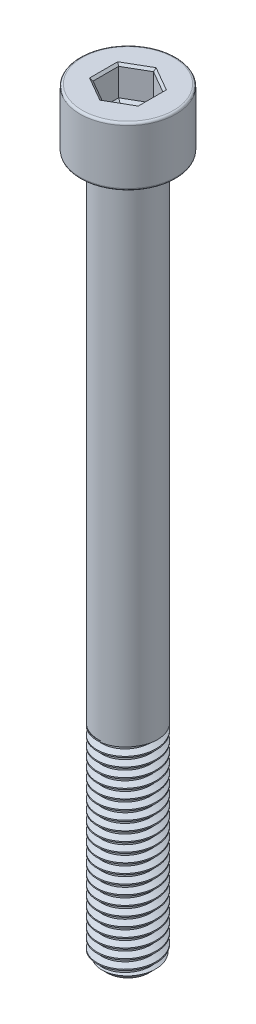
SolidWorks part; units mm, degrees
material "AISI Type A2 Tool Steel"
ref_plane "Front Plane" through (0, 0, 0) normal (0, 0, 1) x (1, 0, 0)
ref_plane "Top Plane" through (0, 0, 0) normal (0, 1, 0) x (1, 0, 0)
ref_plane "Right Plane" through (0, 0, 0) normal (1, 0, 0) x (0, 0, -1)
sketch "Sketch1" plane through (0, 0, 0) normal (0, 1, 0) x (1, 0, 0)
  circle A0 centre (0, 0) radius 4
  dimension "D1" = 8
extrude "Boss-Extrude1" add sketch "Sketch1" along normal blind 28
thread "Thread1" pitch 1.25 method cut profile "Thread Profile1" start angle 0, offset 2, length 0, pitch 1.25, diameter 8
ref_plane "Plane1" through (-4, 30, 0) normal (0, 0, 1) x (-1, 0, 0)
sketch "Thread Profile1" plane through (-4, 30, 0) normal (0, 0, 1) x (-1, 0, 0)
  line L0 (0, 0) -> (0, 1.25) construction
  line L11 (0, 0) -> (0, 1.0937)
  line L12 (0, 1.0937) -> (-0.6766, 0.7031)
  line L13 (-0.6766, 0.7031) -> (-0.6766, 0.3906)
  line L15 (-0.6766, 0.3906) -> (0, 0)
  line L17 (-0.6766, 0.5469) -> (0, 0.5469) construction
  point P2 (0, 0)
  dimension "Pitch" = 1.25
  dimension "Profile_Angle" = 60
  dimension "Profile_Land" = 0.3125
  dimension "Profile_Height" = 0.6766
sketch "Sketch2" plane through (0, 28, 0) normal (0, 1, 0) x (1, 0, 0)
  circle A0 centre (0, 0) radius 4
  dimension "D1" = 8
extrude "Boss-Extrude2" add sketch "Sketch2" along normal blind 67
sketch "Sketch5" plane through (0, 95, 0) normal (0, 1, 0) x (1, 0, 0)
  circle A0 centre (0, 0) radius 6.5
  dimension "D1" = 13
extrude "Boss-Extrude3" add sketch "Sketch5" along normal blind 8
sketch "Sketch6" plane through (0, 0, 0) normal (0, 0, 1) x (1, 0, 0)
  line L0 (0, 0) -> (0, 0.7245) construction
  line L1 (0, 0) -> (4.01, 0) construction
  line L2 (4.01, 0) -> (4.01, 1.2)
  line L3 (4.01, 1.2) -> (2.81, 0)
  line L4 (2.81, 0) -> (4.01, 0)
  dimension "D1" = 1.2
  dimension "D2" = 45
  dimension "D3" = 4.01
revolve "Cut-Revolve1" cut sketch "Sketch6" angle 360 about L0
fillet "Fillet1" radius 0.3 2 edges at (0, 95, 6.5) (0, 103, 6.5)
sketch "Sketch7" plane through (0, 103, 0) normal (0, 1, 0) x (1, 0, 0)
  line L1 (0, 3.4641) -> (-3, 1.7321)
  line L2 (-3, 1.7321) -> (-3, -1.7321)
  line L3 (-3, -1.7321) -> (0, -3.4641)
  line L4 (0, -3.4641) -> (3, -1.7321)
  line L5 (3, -1.7321) -> (3, 1.7321)
  line L6 (3, 1.7321) -> (0, 3.4641)
  circle A0 centre (0, 0) radius 3 construction
  dimension "D1" = 6
extrude "Cut-Extrude1" cut sketch "Sketch7" against normal blind 4
chamfer "Chamfer1" distance 0.3 angle 45 6 edges at (-3, 103, 0) (-1.5, 103, 2.5981) (1.5, 103, 2.5981) (3, 103, 0) (1.5, 103, -2.5981) (-1.5, 103, -2.5981)
sketch "Sketch8" plane through (0, 99, 0) normal (0, 1, 0) x (1, 0, 0)
  line L1 (0, 3.4641) -> (-3, 1.7321)
  line L2 (-3, 1.7321) -> (-3, -1.7321)
  line L3 (-3, -1.7321) -> (0, -3.4641)
  line L4 (0, -3.4641) -> (3, -1.7321)
  line L5 (3, -1.7321) -> (3, 1.7321)
  line L6 (3, 1.7321) -> (0, 3.4641)
  circle A0 centre (0, 0) radius 3 construction
extrude "Cut-Extrude2" cut sketch "Sketch8" against normal blind 0.4 draft 60
